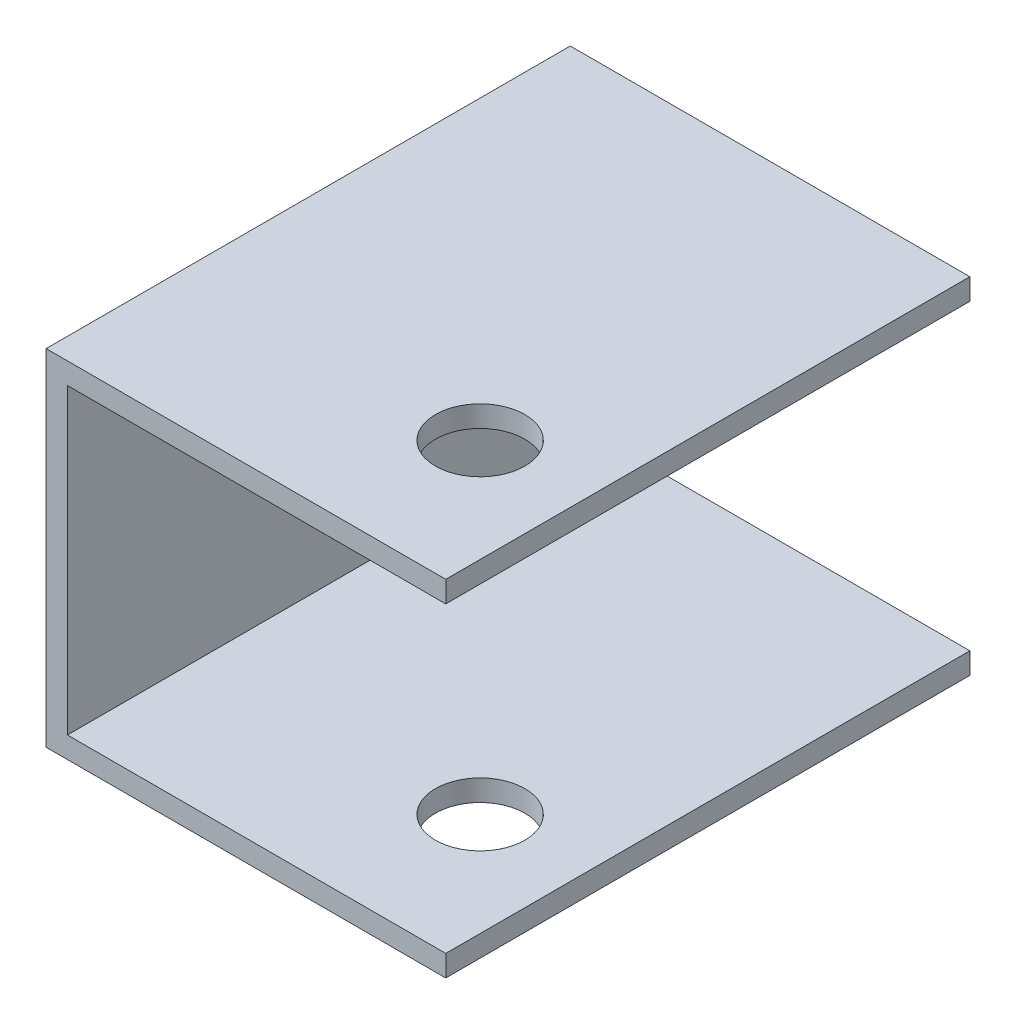
SolidWorks part; units mm, degrees
ref_plane "Alzado" through (0, 0, 0) normal (0, 0, 1) x (1, 0, 0)
ref_plane "Planta" through (0, 0, 0) normal (0, 1, 0) x (1, 0, 0)
ref_plane "Vista lateral" through (0, 0, 0) normal (1, 0, 0) x (0, 0, -1)
sketch "Croquis6" plane through (0, 0, 0) normal (0, 0, 1) x (1, 0, 0)
  line L0 (55, 22) -> (0, 22)
  line L1 (0, 22) -> (0, -22)
  line L2 (0, -22) -> (55, -22)
  line L3 (55, -22) -> (55, -25.1)
  line L4 (55, -25.1) -> (-3.1, -25.1)
  line L5 (-3.1, -25.1) -> (-3.1, 25.1)
  line L6 (-3.1, 25.1) -> (55, 25.1)
  line L7 (55, 25.1) -> (55, 22)
  point P3 (0, 0)
  dimension "D1" = 3.1
  dimension "D2" = 3.1
  dimension "D3" = 3.1
  dimension "D4" = 44
  dimension "D5" = 55
extrude "Saliente-Extruir3" add sketch "Croquis6" along normal mid plane 76.2
sketch "Croquis7" plane through (-3.1, 0, 0) normal (-1, 0, 0) x (0, 0, 1)
  circle A0 centre (0, 0) radius 6.5
  dimension "D1" = 13
extrude "Cortar-Extruir1" cut sketch "Croquis7" against normal blind 5 contours A0
sketch "Croquis8" plane through (0, -25.1, 0) normal (0, -1, 0) x (1, 0, 0)
  line L0 (0, 0) -> (31.2543, 0) construction
  line L1 (-3.1, 38.1) -> (55, 38.1) construction
  line L2 (55, 38.1) -> (55, -38.1) construction
  circle A0 centre (40, 18.1) radius 6.5
  point P4 (40, 0)
  point P6 (40, 23.2326)
  point P7 (0, 0)
  point P10 (40, 21.2304)
  point P11 (40, 17.512)
  dimension "D1" = 13
  dimension "D2" = 15
  dimension "D3" = 20
extrude "Cortar-Extruir2" cut sketch "Croquis8" against normal blind 70 contours A0
